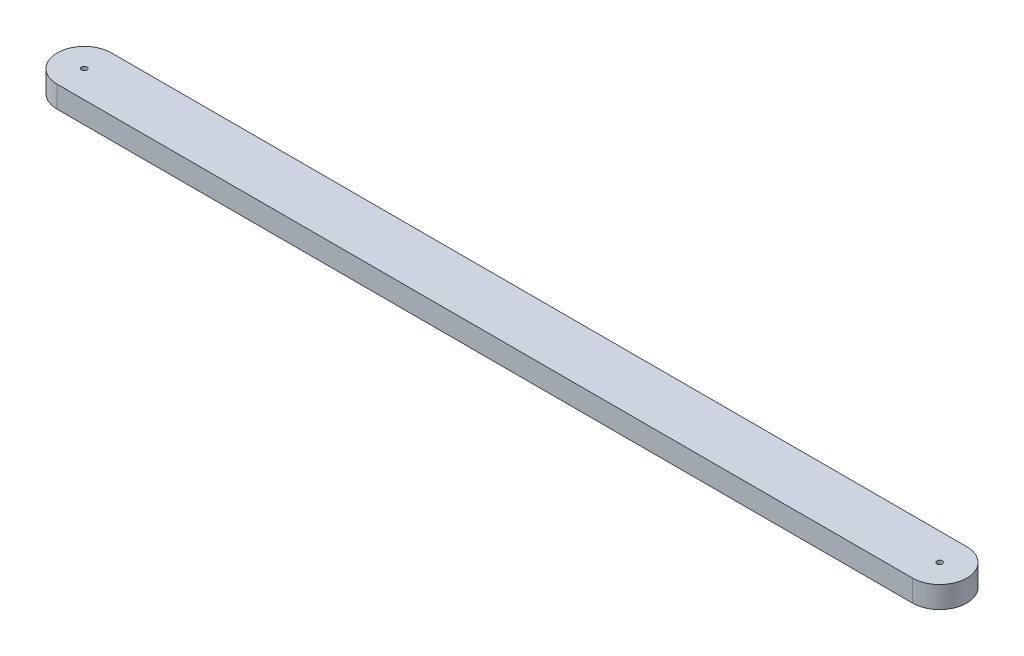
SolidWorks part; units mm, degrees
material "6061-T4 (SS)"
ref_plane "Front Plane" through (0, 0, 0) normal (0, 0, 1) x (1, 0, 0)
ref_plane "Top Plane" through (0, 0, 0) normal (0, 1, 0) x (1, 0, 0)
ref_plane "Right Plane" through (0, 0, 0) normal (1, 0, 0) x (0, 0, -1)
sketch "Sketch1" plane through (0, 0, 0) normal (0, 1, 0) x (1, 0, 0)
  line L0 (-78.805, -5) -> (-78.805, 5)
  line L1 (-78.805, -5) -> (78.805, -5)
  line L2 (-78.805, 5) -> (78.805, 5)
  line L3 (78.805, -5) -> (78.805, 5)
  line L4 (-78.805, -5) -> (78.805, 5) construction
  line L5 (-78.805, 5) -> (78.805, -5) construction
  arc A0 (-78.805, 5) -> (-78.805, -5) centre (-78.805, 0) ccw
  arc A1 (78.805, 5) -> (78.805, -5) centre (78.805, 0) cw
  circle A2 centre (-78.805, 0) radius 0.5
  circle A3 centre (78.805, 0) radius 0.5
  point P1 (0, 0)
  dimension "D1" = 157.61
  dimension "D2" = 10
extrude "Boss-Extrude1" add sketch "Sketch1" along normal blind 2 and the other way blind 2 contours L1 L3 L2 L0 | L0 A0 | A1 L3 region at (-80.9464, 0, 0) region at (0, 0, 0) region at (80.9464, 0, 0)
